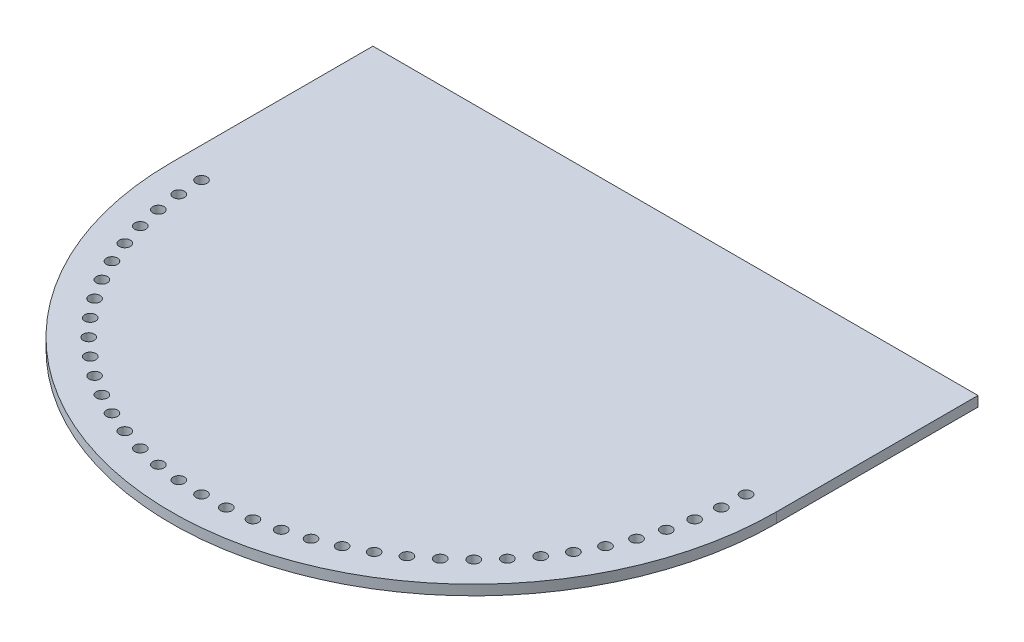
SolidWorks part; units mm, degrees
ref_plane "Front Plane" through (0, 0, 0) normal (0, 0, 1) x (1, 0, 0)
ref_plane "Top Plane" through (0, 0, 0) normal (0, 1, 0) x (1, 0, 0)
ref_plane "Right Plane" through (0, 0, 0) normal (1, 0, 0) x (0, 0, -1)
sketch "Sketch1" plane through (0, 0, 0) normal (0, 1, 0) x (1, 0, 0)
  line L0 (150, 0) -> (-150, 0) construction
  line L2 (-150, 0) -> (-150, 100)
  line L3 (-150, 100) -> (150, 100)
  line L4 (150, 0) -> (150, 100)
  line L5 (0, 100) -> (0, -150) construction
  arc A1 (-150, 0) -> (150, 0) centre (0, 0) ccw
  circle A2 centre (135, 0) radius 2.75
  circle A3 centre (134.4863, -11.766) radius 2.75
  circle A4 centre (132.949, -23.4425) radius 2.75
  circle A5 centre (130.4, -34.9406) radius 2.75
  circle A6 centre (126.8585, -46.1727) radius 2.75
  circle A7 centre (122.3516, -57.0535) radius 2.75
  circle A8 centre (116.9134, -67.5) radius 2.75
  circle A9 centre (110.5855, -77.4328) radius 2.75
  circle A10 centre (103.416, -86.7763) radius 2.75
  circle A11 centre (95.4594, -95.4594) radius 2.75
  circle A12 centre (86.7763, -103.416) radius 2.75
  circle A13 centre (77.4328, -110.5855) radius 2.75
  circle A14 centre (67.5, -116.9134) radius 2.75
  circle A15 centre (57.0535, -122.3516) radius 2.75
  circle A16 centre (46.1727, -126.8585) radius 2.75
  circle A17 centre (34.9406, -130.4) radius 2.75
  circle A18 centre (23.4425, -132.949) radius 2.75
  circle A19 centre (11.766, -134.4863) radius 2.75
  circle A20 centre (0, -135) radius 2.75
  circle A21 centre (-11.766, -134.4863) radius 2.75
  circle A22 centre (-23.4425, -132.949) radius 2.75
  circle A23 centre (-34.9406, -130.4) radius 2.75
  circle A24 centre (-46.1727, -126.8585) radius 2.75
  circle A25 centre (-57.0535, -122.3516) radius 2.75
  circle A26 centre (-67.5, -116.9134) radius 2.75
  circle A27 centre (-77.4328, -110.5855) radius 2.75
  circle A28 centre (-86.7763, -103.416) radius 2.75
  circle A29 centre (-95.4594, -95.4594) radius 2.75
  circle A30 centre (-103.416, -86.7763) radius 2.75
  circle A31 centre (-110.5855, -77.4328) radius 2.75
  circle A32 centre (-116.9134, -67.5) radius 2.75
  circle A33 centre (-122.3516, -57.0535) radius 2.75
  circle A34 centre (-126.8585, -46.1727) radius 2.75
  circle A35 centre (-130.4, -34.9406) radius 2.75
  circle A36 centre (-132.949, -23.4425) radius 2.75
  circle A37 centre (-134.4863, -11.766) radius 2.75
  circle A38 centre (-135, 0) radius 2.75
  point P85 (0, 0)
  dimension "D2" = 300
  dimension "D3" = 37
extrude "Boss-Extrude1" add sketch "Sketch1" along normal blind 5
